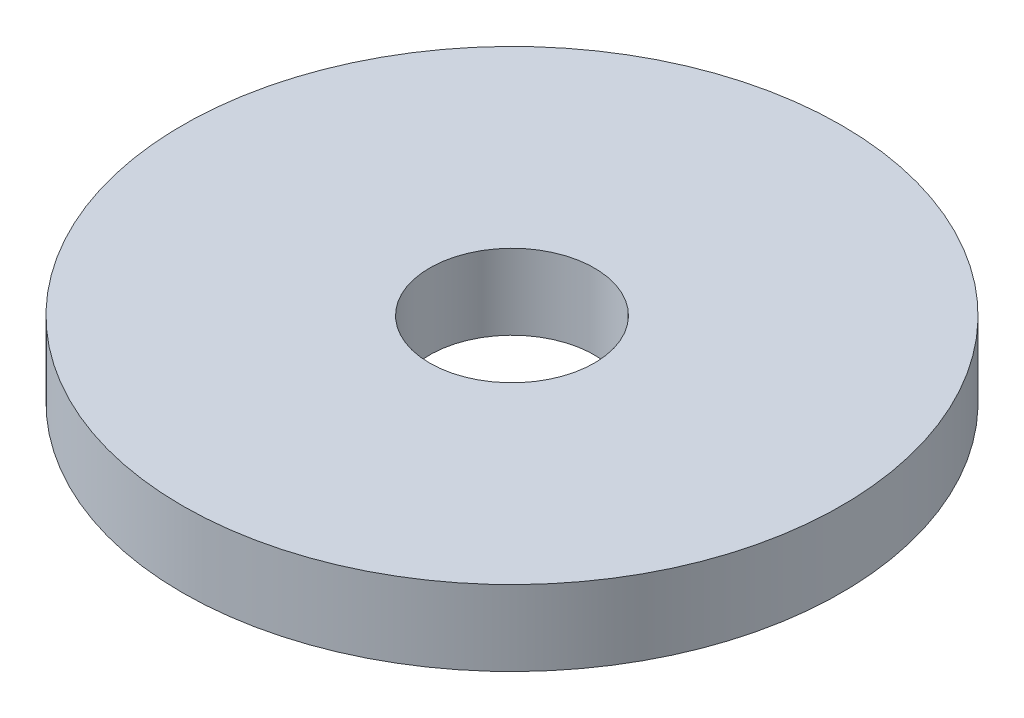
SolidWorks part; units mm, degrees
ref_plane "Front Plane" through (0, 0, 0) normal (0, 0, 1) x (1, 0, 0)
ref_plane "Top Plane" through (0, 0, 0) normal (0, 1, 0) x (1, 0, 0)
ref_plane "Right Plane" through (0, 0, 0) normal (1, 0, 0) x (0, 0, -1)
sketch "Sketch1" plane through (0, 0, 0) normal (0, 1, 0) x (1, 0, 0)
  circle A0 centre (0, 0) radius 70
  dimension "FLANGE_OD" = 140
extrude "Boss-Extrude1" add sketch "Sketch1" along normal blind 16
sketch "Sketch2" plane through (0, 0, 0) normal (0, 1, 0) x (1, 0, 0)
  circle A0 centre (0, 0) radius 17.5
  dimension "BORE_D" = 35
extrude "Cut-Extrude1" cut sketch "Sketch2" along normal through all
sketch "Sketch3" plane through (0, 16, 0) normal (0, 1, 0) x (1, 0, 0)
  circle A0 centre (0, 0) radius 10.6377 construction
  circle A1 centre (-10.6377, 0) radius 2.6663
  dimension "BOLT_D" = 5.3326
  dimension "BOLT_PCD" = 21.2755
extrude "Cut-Extrude2" cut sketch "Sketch3" against normal blind 11.7579 rebuild error yes
pattern_circular "CirPattern1" count 8 over 360 rebuild error yes
